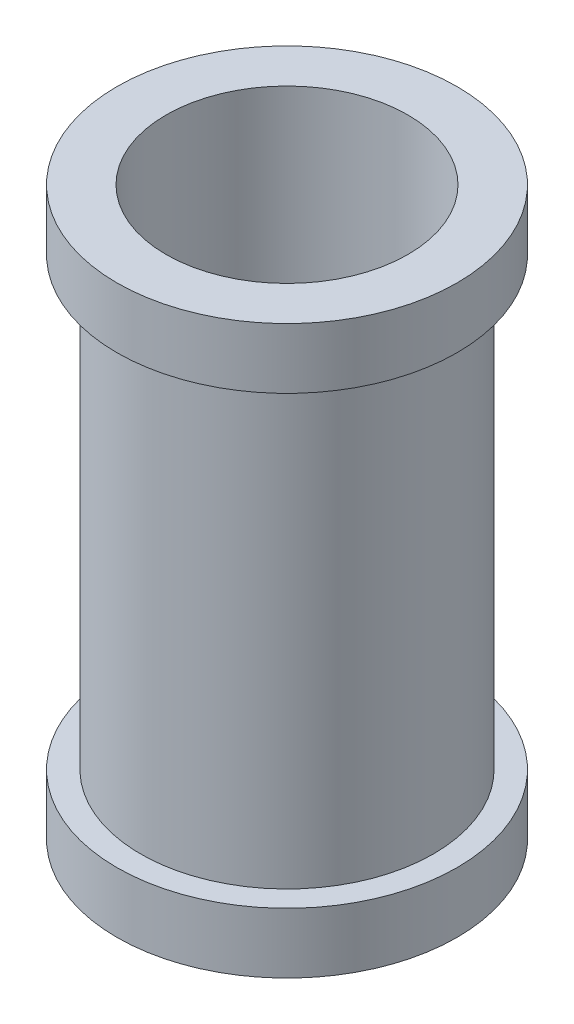
SolidWorks part; units mm, degrees
ref_plane "Front Plane" through (0, 0, 0) normal (0, 0, 1) x (1, 0, 0)
ref_plane "Top Plane" through (0, 0, 0) normal (0, 1, 0) x (1, 0, 0)
ref_plane "Right Plane" through (0, 0, 0) normal (1, 0, 0) x (0, 0, -1)
sketch "Sketch1" plane through (0, 0, 0) normal (0, 1, 0) x (1, 0, 0)
  circle A0 centre (0, 0) radius 20.32
  circle A1 centre (0, 0) radius 0.5
  circle A2 centre (0, 0) radius 24.6062
  dimension "D1" = 49.2125
  dimension "D2" = 40.64
extrude "Boss-Extrude1" add sketch "Sketch1" along normal blind 95.25 contours A2 A0 region at (-23.9103, 0, 0)
sketch "Sketch2" plane through (0, 95.25, 0) normal (0, 1, 0) x (1, 0, 0)
  circle A0 centre (0, 0) radius 28.575
  circle A1 centre (0, 0) radius 24.6063
  dimension "D1" = 57.15
extrude "Boss-Extrude2" add sketch "Sketch2" against normal up to surface (95.25 mm away) up to face at (0, 0, 20.32)
sketch "Sketch3" plane through (0, 0, 0) normal (0, 0, 1) x (1, 0, 0)
  line L0 (0, -3.1128) -> (0, 134.5942) construction
  line L1 (-28.575, 95.25) -> (-28.575, 0) construction
  line L2 (28.575, 10.16) -> (-28.575, 10.16)
  line L3 (28.575, 10.16) -> (28.575, 85.09)
  line L4 (28.575, 85.09) -> (-28.575, 85.09)
  line L5 (-28.575, 10.16) -> (-28.575, 85.09)
  line L6 (28.575, 10.16) -> (-28.575, 85.09) construction
  line L7 (28.575, 85.09) -> (-28.575, 10.16) construction
  point P1 (0, 47.625)
  dimension "D1" = 10.16
  dimension "D2" = 10.16
extrude "Cut-Extrude1" cut sketch "Sketch3" against normal through all both and the other way through all
sketch "Sketch4" plane through (0, 10.16, 0) normal (0, 1, 0) x (1, 0, 0)
  circle A0 centre (0, 0) radius 24.6062
  circle A1 centre (0, 0) radius 20.32
  dimension "D1" = 49.2125
extrude "Boss-Extrude3" add sketch "Sketch4" along normal up to surface (74.93 mm away) up to face at (-20.32, 85.09, 0)
